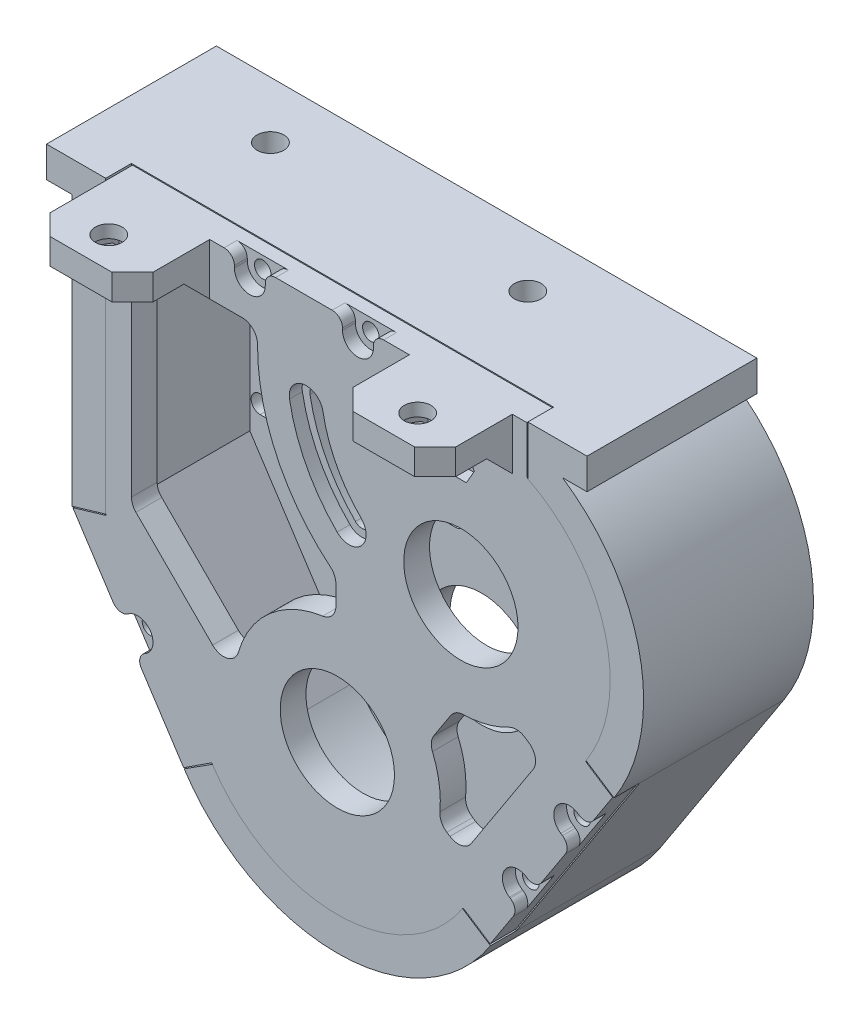
SolidWorks part; units mm, degrees
ref_plane "Front Plane" through (0, 0, 0) normal (0, 0, 1) x (1, 0, 0)
ref_plane "Top Plane" through (0, 0, 0) normal (0, 1, 0) x (1, 0, 0)
ref_plane "Right Plane" through (0, 0, 0) normal (1, 0, 0) x (0, 0, -1)
sketch "Sketch1" plane through (0, 0, 0) normal (0, 0, 1) x (1, 0, 0)
  line L0 (-19, -15.5) -> (-12, -15.5) construction
  line L1 (-21, -21) -> (21, -21)
  line L2 (-21, -21) -> (-21, 21)
  line L3 (-21, 21) -> (21, 21)
  line L4 (21, -21) -> (21, 21)
  line L5 (-21, -21) -> (21, 21) construction
  line L6 (-21, 21) -> (21, -21) construction
  line L7 (-15.5, -15.5) -> (15.5, -15.5) construction
  line L8 (-15.5, -15.5) -> (-15.5, 15.5) construction
  line L9 (-15.5, 15.5) -> (15.5, 15.5) construction
  line L10 (15.5, -15.5) -> (15.5, 15.5) construction
  line L11 (-15.5, -15.5) -> (15.5, 15.5) construction
  line L12 (-15.5, 15.5) -> (15.5, -15.5) construction
  line L13 (-19, -13.75) -> (-12, -13.75)
  line L14 (-19, -17.25) -> (-12, -17.25)
  line L15 (12, -15.5) -> (19, -15.5) construction
  line L16 (12, -13.75) -> (19, -13.75)
  line L17 (12, -17.25) -> (19, -17.25)
  line L18 (12, 15.5) -> (19, 15.5) construction
  line L19 (12, 17.25) -> (19, 17.25)
  line L20 (12, 13.75) -> (19, 13.75)
  line L21 (-19, 15.5) -> (-12, 15.5) construction
  line L22 (-19, 17.25) -> (-12, 17.25)
  line L23 (-19, 13.75) -> (-12, 13.75)
  line L24 (-3.5, 0) -> (3.5, 0) construction
  line L25 (-3.5, 11.1) -> (3.5, 11.1)
  line L26 (-3.5, -11.1) -> (3.5, -11.1)
  line L27 (-21, 29) -> (77, 29)
  line L28 (77, 29) -> (77, 0)
  line L29 (72.3061, -15.8182) -> (48.3061, -52.6964)
  line L30 (-21, -21) -> (-0.2829, -52.732)
  line L31 (-21, 29) -> (-21, 21)
  arc A5 (-19, -13.75) -> (-19, -17.25) centre (-19, -15.5) ccw
  arc A6 (-12, -17.25) -> (-12, -13.75) centre (-12, -15.5) ccw
  arc A7 (12, -13.75) -> (12, -17.25) centre (12, -15.5) ccw
  arc A8 (19, -17.25) -> (19, -13.75) centre (19, -15.5) ccw
  arc A9 (12, 17.25) -> (12, 13.75) centre (12, 15.5) ccw
  arc A10 (19, 13.75) -> (19, 17.25) centre (19, 15.5) ccw
  arc A11 (-19, 17.25) -> (-19, 13.75) centre (-19, 15.5) ccw
  arc A12 (-12, 13.75) -> (-12, 17.25) centre (-12, 15.5) ccw
  arc A13 (-3.5, 11.1) -> (-3.5, -11.1) centre (-3.5, 0) ccw
  arc A14 (3.5, -11.1) -> (3.5, 11.1) centre (3.5, 0) ccw
  circle A15 centre (48, 0) radius 11.1
  circle A16 centre (24, -36.8782) radius 11.1
  circle A17 centre (48, 0) radius 29
  circle A18 centre (24, -36.8782) radius 29
  arc A19 (77, 0) -> (72.3297, -15.7819) centre (48, 0) cw
  arc A20 (48.3061, -52.6964) -> (-0.2829, -52.732) centre (24, -36.8782) cw
  point P0 (0, 0)
  point P6 (0, 0)
  point P13 (-15.5, -15.5)
  point P21 (15.5, -15.5)
  point P28 (15.5, 15.5)
  point P35 (-15.5, 15.5)
  point P41 (0, 0)
  dimension "D3" = 7
  dimension "D6" = 11.1
  dimension "D7" = 22.2
  dimension "D12" = 58
  dimension "D1" = 42
  dimension "D2" = 31
  dimension "D4" = 3.5
  dimension "D5" = 7
  dimension "D8" = 48
  dimension "D9" = 44
  dimension "D10" = 24
  dimension "D11" = 29
extrude "Boss-Extrude1" add sketch "Sketch1" along normal blind 5 contours A18 L29 A17 | L1 A18 A17 L4 A16 | A17 A18 L4 | A18 A17 L4 A15 | A18 L1 L30 | A17 L27 L31 L3 L4 | A18 A17 L4 L3 L2 L1 A14 L26 A13 L25 A12 L23 A11 L22 A10 L20 A9 L19 A6 L14 A5 L13 | A18 L4 A17 | A17 A18 L1 L4 A8 L17 A7 L16 | L4 A18 A17 region at (-20.406, 0, 0) region at (-9.4232, -29.2106, 0) region at (8.6781, -12.5495, 0) region at (10.3665, -21.8013, 0) region at (7.8809, 24.7106, 0) region at (20.7143, -8.9352, 0) region at (20.1764, 0.3657, 0) region at (57.8644, -32.6683, 0) region at (36.0473, -18.4685, 0) region at (32.1117, 23.2928, 0)
sketch "Sketch3" plane through (0, 0, 0) normal (0, 0, -1) x (-1, 0, 0)
  line L0 (27.5, -22.934) -> (27.5, 35.5)
  line L1 (27.5, 35.5) -> (-48, 35.5)
  line L2 (-77.754, -19.3636) -> (-53.754, -56.2418)
  line L3 (5.7256, -56.2854) -> (27.5, -22.934)
  line L8 (21, -21) -> (21, 29)
  line L9 (21, 29) -> (-48, 29)
  line L10 (-72.3061, -15.8182) -> (-48.3061, -52.6964)
  line L11 (0.2829, -52.732) -> (21, -21)
  line L12 (21, -21) -> (21, 29)
  line L13 (21, 29) -> (-48, 29)
  line L14 (-72.3061, -15.8182) -> (-48.3061, -52.6964)
  line L15 (0.2829, -52.732) -> (21, -21)
  arc A0 (-48, 35.5) -> (-77.754, -19.3636) centre (-48, 0) ccw
  arc A1 (-53.754, -56.2418) -> (5.7256, -56.2854) centre (-24, -36.8782) ccw
  arc A4 (-48, 29) -> (-72.3061, -15.8182) centre (-48, 0) ccw
  arc A5 (-48.3061, -52.6964) -> (0.2829, -52.732) centre (-24, -36.8782) ccw
  arc A6 (-48, 29) -> (-72.3061, -15.8182) centre (-48, 0) ccw
  arc A7 (-48.3061, -52.6964) -> (0.2829, -52.732) centre (-24, -36.8782) ccw
  dimension "D1" = 0
  dimension "D2" = 6.5
extrude "Boss-Extrude2" add sketch "Sketch3" against normal blind 28
sketch "Sketch4" plane through (0, 35.5, 0) normal (0, 1, 0) x (1, 0, 0)
  line L0 (48, -28) -> (83.5, -28) construction
  line L1 (-32.5, 0) -> (72.5, 0)
  line L2 (-32.5, 0) -> (-32.5, -28)
  line L3 (-32.5, -28) -> (72.5, -28)
  line L4 (72.5, 0) -> (72.5, -28)
  line L5 (-27.5, -28) -> (-27.5, 0) construction
  dimension "D1" = 105
  dimension "D2" = 5
extrude "Boss-Extrude3" add sketch "Sketch4" against normal blind 6
sketch "Sketch5" plane through (0, 0, 28) normal (0, 0, 1) x (1, 0, 0)
  line L0 (-21, 29) -> (-21, 35.5)
  line L1 (-32.5, 35.5) -> (72.5, 35.5) construction
  line L2 (61, 25.923) -> (61, 35.5)
  line L3 (72.5, 29.5) -> (72.5, 35.5) construction
  line L4 (61, 35.5) -> (67.7484, 29.5)
  line L6 (72.3061, -15.8182) -> (77.754, -19.3636)
  line L7 (48.3061, -52.6964) -> (53.754, -56.2418)
  line L9 (-0.2829, -52.732) -> (-5.754, -56.2418)
  line L10 (-27.5, -22.934) -> (-21, -21)
  line L11 (-27.5, -22.934) -> (-27.5, 29.5) construction
  line L12 (-21, 35.5) -> (-27.5, 35.5)
  line L13 (-27.5, 35.5) -> (-27.5, -22.934)
  line L14 (-27.5, 29.5) -> (-32.5, 29.5)
  line L15 (-32.5, 29.5) -> (-32.5, 35.5)
  line L16 (-32.5, 35.5) -> (-27.5, 35.5)
  line L17 (67.7484, 29.5) -> (72.5, 29.5)
  line L18 (72.5, 29.5) -> (72.5, 35.5)
  line L19 (72.5, 35.5) -> (61, 35.5)
  arc A0 (72.3061, -15.8182) -> (48, 29) centre (48, 0) ccw construction
  arc A1 (77.754, -19.3636) -> (67.7484, 29.5) centre (48, 0) ccw construction
  arc A2 (77.754, -19.3636) -> (67.7484, 29.5) centre (48, 0) ccw
  arc A3 (72.3061, -15.8182) -> (48, 29) centre (48, 0) ccw construction
  arc A4 (72.3061, -15.8182) -> (48, 29) centre (48, 0) ccw
  arc A5 (-5.7256, -56.2854) -> (53.754, -56.2418) centre (24, -36.8782) ccw construction
  arc A6 (-0.2829, -52.732) -> (48.3061, -52.6964) centre (24, -36.8782) ccw construction
  arc A7 (-0.2829, -52.732) -> (48.3061, -52.6964) centre (24, -36.8782) ccw
  arc A8 (-5.754, -56.2418) -> (53.754, -56.2418) centre (24, -36.8782) ccw
  line M2 (72.5, 35.5) -> (-32.5, 35.5)
  line M3 (-32.5, 35.5) -> (-32.5, 29.5)
  line M4 (-32.5, 29.5) -> (-27.5, 29.5)
  line M5 (-27.5, 29.5) -> (-27.5, -22.934)
  arc M7 (-5.7256, -56.2854) -> (53.754, -56.2418) centre (24, -36.8782) ccw
  arc M9 (77.754, -19.3636) -> (67.7484, 29.5) centre (48, 0) ccw
  line M10 (67.7484, 29.5) -> (72.5, 29.5)
  line M11 (72.5, 29.5) -> (72.5, 35.5)
  arc M12 (48.3061, -52.6964) -> (-0.2829, -52.732) centre (24, -36.8782) cw
  line M14 (-21, -21) -> (-21, 29)
  arc M16 (48, 29) -> (72.3061, -15.8182) centre (48, 0) cw
  dimension "D1" = 11.5
extrude "Boss-Extrude4" add sketch "Sketch5" along normal blind 5 contours L13 M2 M3 M4 | L13 L0 M2 M5 M14 | L4 M2 M10 M11 | L6 L4 L2 M16 M9 | L9 A8 L7 M7 M12 region at (-24.2682, 6.7638, 28) region at (68.2036, 32.9152, 28) region at (63.9802, 32.0568, 28) region at (-30, 32.5, 28) region at (50.6881, -54.9944, 28)
sketch "Sketch6" plane through (0, 0, 33) normal (0, 0, 1) x (1, 0, 0)
  line L0 (-0.2829, -52.732) -> (-5.754, -56.2418) construction
  line L1 (-27.5, -22.934) -> (-21, -21) construction
  line L2 (-27.5, -22.934) -> (-21, -21) construction
  line L3 (48.5828, -52.6378) -> (48.3061, -52.6964)
  line L4 (72.3646, -16.0949) -> (72.3061, -15.8182)
  line L5 (60.8, 26.245) -> (61, 25.923)
  line L6 (-20.8, 29.2) -> (-21, 29)
  line L8 (60.8, 26.245) -> (60.8, 35.3)
  line L9 (60.8, 35.3) -> (-20.8, 35.3)
  line L10 (-20.8, 35.3) -> (-20.8, 29.2)
  line L11 (-20.8, 29.2) -> (48, 29.2)
  line L12 (60.8, 26.245) -> (60.8, 35.3)
  line L13 (60.8, 35.3) -> (-20.8, 35.3)
  line L14 (-20.8, 35.3) -> (-20.8, 29.2)
  line L15 (-20.8, 29.2) -> (48, 29.2)
  line L16 (-20.8859, -21.1747) -> (-27.3859, -23.1087)
  line L17 (-5.7256, -56.2854) -> (-27.5, -22.934) construction
  line L24 (-27.3859, -23.1087) -> (-5.8491, -56.0961)
  line L25 (-5.8491, -56.0961) -> (-0.4064, -52.5427)
  line L26 (72.3646, -16.0949) -> (48.5828, -52.6378)
  line L27 (48.5828, -52.6378) -> (53.6954, -55.9651)
  line L28 (53.6954, -55.9651) -> (77.4773, -19.4222)
  line L29 (77.4773, -19.4222) -> (72.3646, -16.0949)
  line L30 (72.3646, -16.0949) -> (48.5828, -52.6378)
  line L31 (48.5828, -52.6378) -> (53.6954, -55.9651)
  line L32 (53.6954, -55.9651) -> (77.4773, -19.4222)
  line L33 (77.4773, -19.4222) -> (72.3646, -16.0949)
  line L83 (-21, 29) -> (-21, -21)
  line L84 (-21, -21) -> (-0.2829, -52.732)
  line L85 (48.3061, -52.6964) -> (72.3061, -15.8182)
  line L86 (48, 29) -> (-21, 29)
  line L87 (-21, 29) -> (-21, -21)
  line L88 (-21, -21) -> (-0.2829, -52.732)
  line L89 (48.3061, -52.6964) -> (72.3061, -15.8182)
  line L90 (48, 29) -> (-21, 29)
  arc A2 (60.8, 26.245) -> (48, 29.2) centre (48, 0) ccw
  arc A3 (60.8, 26.245) -> (48, 29.2) centre (48, 0) ccw
  arc A8 (-0.2829, -52.732) -> (48.3061, -52.6964) centre (24, -36.8782) ccw
  arc A9 (72.3061, -15.8182) -> (48, 29) centre (48, 0) ccw
  arc A10 (-0.2829, -52.732) -> (48.3061, -52.6964) centre (24, -36.8782) ccw
  arc A11 (72.3061, -15.8182) -> (48, 29) centre (48, 0) ccw
  point P18 (-3.0184, -54.4869)
  arc M15 (48.3061, -52.6964) -> (-0.2829, -52.732) centre (24, -36.8782) cw
  dimension "D4" = 0.2
  dimension "D5" = 0.2
  dimension "D1" = 0
  dimension "D2" = 0.2
  dimension "D3" = 0.2
extrude "Boss-Extrude6" add sketch "Sketch6" against normal up to surface (5 mm away) separate body contours A11 L90 L87 L88 L89 M15 | L88 L16 L24 L25 | L32 L33 L30 L31 | L89 L3 L30 L4 | A11 L5 A3 L15 L6 L90 | A3 L12 L13 L14 L15 region at (60.3898, -34.3117, 33) region at (63.03, -36.03, 33) region at (25.1336, -11.9336, 33) region at (54.6985, 28.3001, 33) region at (-13.6569, -38.2421, 33) region at (20.9105, 32.155, 33) up to face at (-12.0525, -41.8386, 28)
sketch "Sketch7" plane through (0, 0, 33) normal (0, 0, 1) x (1, 0, 0)
  circle A0 centre (24, -36.8782) radius 11.1 construction
  circle A1 centre (48, 0) radius 11.1 construction
  circle A2 centre (24, -36.8782) radius 11.1
  circle A3 centre (48, 0) radius 11.1
extrude "Cut-Extrude1" cut sketch "Sketch7" against normal up to next (5 mm away)
sketch "Sketch8" plane through (0, 0, 33) normal (0, 0, 1) x (1, 0, 0)
  line L1 (50.6177, 22) -> (49.0588, 24.7)
  line L2 (49.0588, 24.7) -> (45.9412, 24.7)
  line L3 (45.9412, 24.7) -> (44.3823, 22)
  line L4 (44.3823, 22) -> (45.9412, 19.3)
  line L5 (45.9412, 19.3) -> (49.0588, 19.3)
  line L6 (49.0588, 19.3) -> (50.6177, 22)
  circle A0 centre (47.5, 22) radius 2.7 construction
  circle A1 centre (47.5, 22) radius 1.85
  dimension "D4" = 3.7
  dimension "D1" = 5.4
  dimension "D2" = 47.5
  dimension "D3" = 22
extrude "Cut-Extrude2" cut sketch "Sketch8" against normal blind 2.5
extrude "Cut-Extrude3" cut sketch "Sketch8<2>" against normal up to next (5 mm away) contours A1 region at (47.5, 22, 33)
sketch "Sketch8<2>" plane through (0, 0, 33) normal (0, 0, 1) x (1, 0, 0) same geometry as "Sketch8"
sketch "Sketch9" plane through (0, 0, 33) normal (0, 0, 1) x (1, 0, 0)
  line L0 (26.2868, 0.7868) -> (47.5, 22) construction
  line L1 (47.5, 22) -> (17.9558, 16.7906) construction
  line L3 (-21, 35.5) -> (61, 35.5) construction
  arc A0 (17.9558, 16.7906) -> (26.2868, 0.7868) centre (47.5, 22) ccw construction
  arc A1 (16.1831, 16.478) -> (25.014, -0.486) centre (47.5, 22) ccw
  arc A2 (19.7284, 17.1031) -> (27.5596, 2.0596) centre (47.5, 22) ccw
  arc A3 (19.7284, 17.1031) -> (16.1831, 16.478) centre (17.9558, 16.7906) ccw
  arc A4 (25.014, -0.486) -> (27.5596, 2.0596) centre (26.2868, 0.7868) ccw
  point P4 (20.8897, 8.1475)
  dimension "D2" = 1.8
  dimension "D3" = 30
  dimension "D1" = 35
  dimension "D4" = 10
extrude "Cut-Extrude4" cut sketch "Sketch9" against normal up to surface (5 mm away) up to face at (45.65, 22, 28)
sketch "Sketch10" plane through (0, 0, 33) normal (0, 0, 1) x (1, 0, 0)
  arc A14 (21.2056, 17.3636) -> (14.7059, 16.2175) centre (17.9558, 16.7906) ccw
  arc A15 (21.2056, 17.3636) -> (28.6202, 3.1202) centre (47.5, 22) ccw
  arc A16 (23.9533, -1.5467) -> (28.6202, 3.1202) centre (26.2868, 0.7868) ccw
  arc A17 (14.7059, 16.2175) -> (23.9533, -1.5467) centre (47.5, 22) ccw
  arc A18 (21.2056, 17.3636) -> (14.7059, 16.2175) centre (17.9558, 16.7906) ccw
  arc A19 (21.2056, 17.3636) -> (28.6202, 3.1202) centre (47.5, 22) ccw
  arc A20 (23.9533, -1.5467) -> (28.6202, 3.1202) centre (26.2868, 0.7868) ccw
  arc A21 (14.7059, 16.2175) -> (23.9533, -1.5467) centre (47.5, 22) ccw
  dimension "D1" = 1.5
extrude "Cut-Extrude5" cut sketch "Sketch10" against normal blind 2.5
sketch "Sketch11" plane through (0, 0, 33) normal (0, 0, 1) x (1, 0, 0)
  line L1 (-20.8, 35.3) -> (58, 35.3)
  line L2 (-20.8, 35.3) -> (-20.8, 30.3)
  line L3 (-20.8, 30.3) -> (58, 30.3)
  line L4 (58, 35.3) -> (58, 30.3)
  line L5 (61, 25.923) -> (61, 35.5) construction
  line L6 (-0.8, 35.3) -> (38, 35.3)
  line L7 (-0.8, 35.3) -> (-0.8, 30.3)
  line L8 (-0.8, 30.3) -> (38, 30.3)
  line L9 (38, 35.3) -> (38, 30.3)
  line M19 (60.8, 26.245) -> (60.8, 35.3)
  line M20 (60.8, 35.3) -> (-20.8, 35.3)
  line M21 (-20.8, 35.3) -> (-20.8, 29.2)
  dimension "D1" = 5
  dimension "D2" = 20
  dimension "D3" = 20
  dimension "D4" = 3
extrude "Boss-Extrude7" add sketch "Sketch11" along normal blind 15 contours L7 L3 M20 M21 | L9 L3 M20 M19 region at (-10.8, 32.8, 33) region at (48, 32.8, 33)
sketch "Sketch12" plane through (0, 0, 33) normal (0, 0, 1) x (1, 0, 0)
  line L0 (7, 32.9115) -> (7, 37.6885) construction
  line L1 (4, 32.9115) -> (4, 37.6885)
  line L2 (10, 32.9115) -> (10, 37.6885)
  line L3 (28, 32.9115) -> (28, 37.6885) construction
  line L4 (25, 32.9115) -> (25, 37.6885)
  line L5 (31, 32.9115) -> (31, 37.6885)
  line L6 (69.0451, -28) -> (73.0489, -30.6057) construction
  line L7 (70.6815, -25.4856) -> (74.6853, -28.0912)
  line L8 (67.4087, -30.5144) -> (71.4126, -33.1201)
  line L9 (53.6954, -55.9651) -> (77.4773, -19.4222) construction
  line L10 (59.0681, -43.6972) -> (63.072, -46.3028) construction
  line L11 (60.7045, -41.1828) -> (64.7083, -43.7884)
  line L12 (57.4318, -46.2116) -> (61.4356, -48.8172)
  line L13 (77.754, -19.3636) -> (53.754, -56.2418) construction
  line L16 (-14.8112, -38) -> (-18.8112, -40.6115) construction
  line L17 (-13.1712, -40.512) -> (-17.1712, -43.1235)
  line L18 (-16.4513, -35.488) -> (-20.4513, -38.0995)
  line L19 (-27.3859, -23.1087) -> (-5.8491, -56.0961) construction
  line L21 (38, 35.3) -> (-0.8, 35.3) construction
  arc A0 (4, 32.9115) -> (10, 32.9115) centre (7, 32.9115) ccw
  arc A1 (10, 37.6885) -> (4, 37.6885) centre (7, 37.6885) ccw
  arc A2 (25, 32.9115) -> (31, 32.9115) centre (28, 32.9115) ccw
  arc A3 (31, 37.6885) -> (25, 37.6885) centre (28, 37.6885) ccw
  arc A4 (70.6815, -25.4856) -> (67.4087, -30.5144) centre (69.0451, -28) ccw
  arc A5 (71.4126, -33.1201) -> (74.6853, -28.0912) centre (73.0489, -30.6057) ccw
  arc A6 (60.7045, -41.1828) -> (57.4318, -46.2116) centre (59.0681, -43.6972) ccw
  arc A7 (61.4356, -48.8172) -> (64.7083, -43.7884) centre (63.072, -46.3028) ccw
  arc A10 (-13.1712, -40.512) -> (-16.4513, -35.488) centre (-14.8112, -38) ccw
  arc A11 (-20.4513, -38.0995) -> (-17.1712, -43.1235) centre (-18.8112, -40.6115) ccw
  circle A12 centre (7, 32.9115) radius 1.6
  circle A13 centre (28, 32.9115) radius 1.6
  circle A14 centre (69.0451, -28) radius 1.6
  circle A15 centre (59.0681, -43.6972) radius 1.6
  circle A16 centre (-14.8112, -38) radius 1.6
  point P2 (7, 35.3)
  point P7 (28, 35.3)
  point P14 (71.047, -29.3028)
  point P21 (61.0701, -45)
  point P37 (-16.8112, -39.3058)
  dimension "D1" = 3
  dimension "D3" = 3.2
  dimension "D2" = 4
  dimension "D4" = 28
  dimension "D5" = 45
  dimension "D6" = 38
  dimension "D7" = 7
  dimension "D8" = 28
extrude "Cut-Extrude6" cut sketch "Sketch12" against normal blind 2.5 contours L2 A1 L1 A0 | L5 A3 L4 A2 | L8 A5 L7 A4 | L12 A7 L11 A6 | L18 A11 L17 A10
extrude "Cut-Extrude7" cut sketch "Sketch12<3>" against normal up to surface (5 mm away) contours A16 | A15 | A14 | A13 | A12 region at (7, 32.9115, 33) region at (28, 32.9115, 33) region at (69.0451, -28, 33) region at (59.0681, -43.6972, 33) region at (-14.8112, -38, 33) up to face at (21.7455, 8.5931, 28)
sketch "Sketch12<3>" plane through (0, 0, 33) normal (0, 0, 1) x (1, 0, 0) same geometry as "Sketch12"
sketch "Sketch13" plane through (0, 0, 33) normal (0, 0, 1) x (1, 0, 0)
  line L0 (23.72, -16.8801) -> (23.72, -8.9114)
  line L1 (4, -36.8782) -> (-16, -16.8782)
  line L2 (-16, -16.8782) -> (-16, 25.3)
  line L3 (-16, 25.3) -> (8.6399, 25.3)
  line L4 (-21, 29) -> (-21, -21) construction
  line L5 (-20.8, 30.3) -> (-0.8, 30.3) construction
  line L6 (46.9339, -19.9716) -> (41.829, -27.8157)
  line L7 (43.6939, -40.364) -> (48.3811, -43.4144)
  line L8 (48.3811, -43.4144) -> (63.6538, -19.9465)
  line L9 (63.6538, -19.9465) -> (58.8353, -16.8106)
  line L10 (77.754, -19.3636) -> (53.754, -56.2418) construction
  arc A0 (23.72, -8.9114) -> (8.6399, 25.3) centre (47.5, 22) cw
  arc A1 (23.72, -16.8801) -> (4, -36.8782) centre (24, -36.8782) ccw
  arc A2 (41.829, -27.8157) -> (43.6939, -40.364) centre (24, -36.8782) cw
  arc A3 (46.9339, -19.9716) -> (58.8353, -16.8106) centre (48, 0) ccw
  dimension "D4" = 39
  dimension "D5" = 20
  dimension "D8" = 20
  dimension "D9" = 20
  dimension "D1" = 135
  dimension "D2" = 5
  dimension "D3" = 5
  dimension "D6" = 7.9688
  dimension "D7" = 5
  dimension "D10" = 14
  dimension "D11" = 28
  dimension "D12" = 9.5
extrude "Cut-Extrude8" cut sketch "Sketch13" against normal up to surface (5 mm away) up to face at (-16.4112, -38, 28)
sketch "Sketch16" plane through (0, 29, 0) normal (0, -1, 0) x (1, 0, 0)
  line L0 (-21, 28) -> (-21, 5) construction
  line L1 (44.5426, 11) -> (41.7713, 15.8)
  line L2 (41.7713, 15.8) -> (36.2287, 15.8)
  line L3 (36.2287, 15.8) -> (33.4574, 11)
  line L4 (33.4574, 11) -> (36.2287, 6.2)
  line L5 (36.2287, 6.2) -> (41.7713, 6.2)
  line L6 (41.7713, 6.2) -> (44.5426, 11)
  line L7 (-5.4574, 11) -> (-8.2287, 15.8)
  line L8 (-8.2287, 15.8) -> (-13.7713, 15.8)
  line L9 (-13.7713, 15.8) -> (-16.5426, 11)
  line L10 (-16.5426, 11) -> (-13.7713, 6.2)
  line L11 (-13.7713, 6.2) -> (-8.2287, 6.2)
  line L12 (-8.2287, 6.2) -> (-5.4574, 11)
  circle A0 centre (39, 11) radius 4.8 construction
  circle A1 centre (-11, 11) radius 4.8 construction
  circle A2 centre (39, 11) radius 2.6
  circle A3 centre (-11, 11) radius 2.6
  dimension "D6" = 5.2
  dimension "D1" = 9.6
  dimension "D2" = 9.6
  dimension "D3" = 10
  dimension "D4" = 50
  dimension "D5" = 11
extrude "Cut-Extrude9" cut sketch "Sketch16" against normal blind 2.5
extrude "Cut-Extrude10" cut sketch "Sketch16<2>" against normal through all contours A3 | A2 region at (39, 29, 11) region at (-11, 29, 11)
sketch "Sketch16<2>" plane through (0, 29, 0) normal (0, -1, 0) x (1, 0, 0) same geometry as "Sketch16"
sketch "Sketch17" plane through (0, 30.3, 0) normal (0, -1, 0) x (1, 0, 0)
  line L0 (-15.1712, 33) -> (-5.8491, 33) construction
  line L1 (-8.6287, 46.8) -> (-14.1713, 46.8)
  line L2 (-14.1713, 46.8) -> (-16.9426, 42)
  line L3 (-16.9426, 42) -> (-14.1713, 37.2)
  line L4 (-14.1713, 37.2) -> (-8.6287, 37.2)
  line L5 (-8.6287, 37.2) -> (-5.8574, 42)
  line L6 (-5.8574, 42) -> (-8.6287, 46.8)
  line L7 (51.3713, 46.8) -> (45.8287, 46.8)
  line L8 (45.8287, 46.8) -> (43.0574, 42)
  line L9 (43.0574, 42) -> (45.8287, 37.2)
  line L10 (45.8287, 37.2) -> (51.3713, 37.2)
  line L11 (51.3713, 37.2) -> (54.1426, 42)
  line L12 (54.1426, 42) -> (51.3713, 46.8)
  line L13 (18.6, 51.3581) -> (18.6, 29.153) construction
  line L14 (38, 48) -> (38, 33) construction
  line L15 (-0.8, 48) -> (-0.8, 33) construction
  circle A0 centre (-11.4, 42) radius 4.8 construction
  circle A1 centre (48.6, 42) radius 4.8 construction
  circle A2 centre (-11.4, 42) radius 2.6
  circle A3 centre (48.6, 42) radius 2.6
  dimension "D5" = 5.2
  dimension "D6" = 5.2
  dimension "D1" = 9.6
  dimension "D2" = 60
  dimension "D3" = 9
  dimension "D4" = 9.6
extrude "Cut-Extrude11" cut sketch "Sketch17" against normal blind 2.5 contours L11 L12 L7 L8 L9 L10 A3 | L5 L6 L1 L2 L3 L4 A2 region at (-7.3701, 30.3, 44.3267) region at (52.6299, 30.3, 44.3267)
extrude "Cut-Extrude12" cut sketch "Sketch17<3>" against normal through all contours A2 | A3 region at (-11.4, 30.3, 42) region at (48.6, 30.3, 42)
sketch "Sketch17<3>" plane through (0, 30.3, 0) normal (0, -1, 0) x (1, 0, 0) same geometry as "Sketch17"
sketch "Sketch18" plane through (0, 0, 28) normal (0, 0, 1) x (1, 0, 0)
  circle A0 centre (69.0451, -28) radius 1.5
  circle A1 centre (59.0681, -43.6972) radius 1.5
  circle A2 centre (28, 32.9115) radius 1.5
  circle A3 centre (7, 32.9115) radius 1.5
  circle A4 centre (-14.8112, -38) radius 1.5
  dimension "D1" = 3
extrude "Cut-Extrude13" cut sketch "Sketch18" against normal blind 8
chamfer "Chamfer1" distance 4 angle 45 4 edges at (-20.8, 32.8, 48) (-0.8, 32.8, 48) (58, 32.8, 48) (38, 32.8, 48)
chamfer "Chamfer2" distance 5 angle 45 2 edges at (48, 30.3, 33) (-10.8, 30.3, 33)
fillet "Fillet3" radius 3 6 edges at (23.72, -8.9114, 30.5) (23.72, -16.8801, 30.5) (4, -36.8782, 30.5) (-16, -16.8782, 30.5) (-16, 25.3, 30.5) (8.6399, 25.3, 30.5)
fillet "Fillet4" radius 3 6 edges at (43.6939, -40.364, 30.5) (41.829, -27.8157, 30.5) (46.9339, -19.9716, 30.5) (63.6538, -19.9465, 30.5) (48.3811, -43.4144, 30.5) (58.8353, -16.8106, 30.5)
fillet "Fillet5" radius 2 10 edges at (4, 35.3, 31.75) (10, 35.3, 31.75) (25, 35.3, 31.75) (31, 35.3, 31.75) (72.6834, -26.7884, 31.75) (69.4107, -31.8172, 31.75) (62.5388, -42.3765, 31.75) (59.2661, -47.4053, 31.75) (-18.4513, -36.7937, 31.75) (-15.1712, -41.8178, 31.75)
